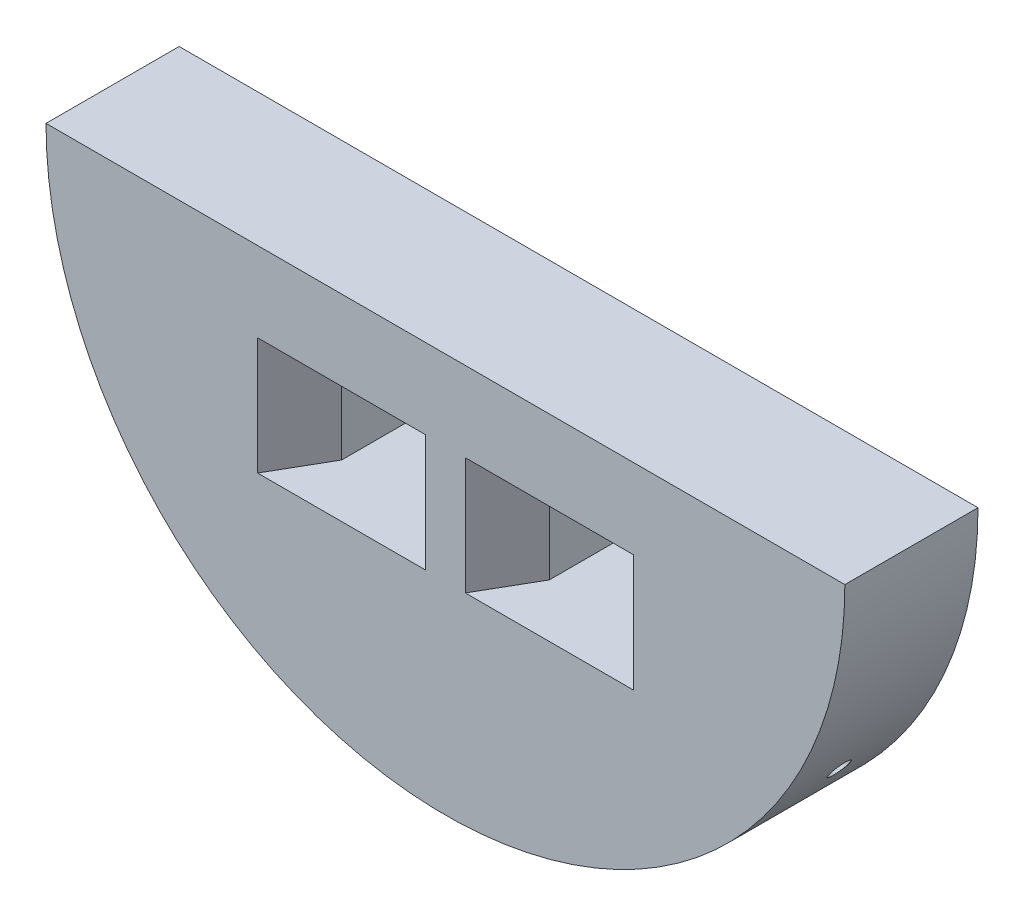
SolidWorks part; units mm, degrees
ref_plane "Front Plane" through (0, 0, 0) normal (0, 0, 1) x (1, 0, 0)
ref_plane "Top Plane" through (0, 0, 0) normal (0, 1, 0) x (1, 0, 0)
ref_plane "Right Plane" through (0, 0, 0) normal (1, 0, 0) x (0, 0, -1)
sketch "Sketch1" plane through (0, 0, 0) normal (0, 0, 1) x (1, 0, 0)
  line L0 (-150, 0) -> (0, 0)
  line L3 (-65.5, -37) -> (-45.5, -37)
  line L4 (-65.5, -37) -> (-65.5, -15)
  line L5 (-65.5, -15) -> (-45.5, -15)
  line L6 (-45.5, -37) -> (-45.5, -15)
  line L7 (-104.5, -37) -> (-84.5, -37)
  line L8 (-104.5, -37) -> (-104.5, -15)
  line L9 (-104.5, -15) -> (-84.5, -15)
  line L10 (-84.5, -37) -> (-84.5, -15)
  arc A1 (-150, 0) -> (0, 0) centre (-75, 0) ccw
  point P0 (-94.5, -15)
  point P13 (-55.5, -15)
  dimension "D1" = 19.5
  dimension "D7" = 75
  dimension "D2" = 15
  dimension "D3" = 19.5
  dimension "D4" = 20
  dimension "D5" = 22
extrude "Boss-Extrude1" add sketch "Sketch1" along normal blind 25
hole_wizard "Ø4.0mm Dowel Hole2" positions "3DSketch2" profile "Sketch4" hole size "Ø4.0" standard "ANSI Metric"
sketch3d "3DSketch2"
  line L2 (0, 0, 25) -> (0, 0, 0) construction
  line L4 (0, 0, 25) -> (0, 0, 0) construction
  line L5 (0, 0, 12.5) -> (-13.5636, -43.0182, 12.5) construction
  line L8 (-75, 0, 0) -> (-75, 0, 25) construction
  line L9 (0, 0, 0) -> (-150, 0, 0) construction
  line L10 (0, 0, 25) -> (-150, 0, 25) construction
  line L12 (-75, 0, 12.5) -> (-13.5636, -43.0182, 12.5) construction
  line L16 (-75, 0, 12.5) -> (0, 0, 12.5) construction
  point P0 (-13.5636, -43.0182, 12.5)
  point P16 (-13.5636, -43.0182, 12.5)
  point P23 (-13.5636, -43.0182, 12.5)
  point P25 (-13.5636, -43.0182, 12.5)
  dimension "D1" = 35
sketch "Sketch4" plane through (-13.5636, -43.0182, 12.5) normal (0, 0, 1) x (0.5736, 0.8192, 0)
  line L0 (0, 0) -> (0, 17.2017)
  line L1 (0, 17.2017) -> (2, 16)
  line L2 (2, 16) -> (2, 0.025)
  line L3 (2, 0.025) -> (2.025, 0)
  line L5 (2.025, 0) -> (0, 0)
  line L6 (-2, 0.025) -> (-2.025, 0) construction
  line L10 (0, 17.2017) -> (-2, 16) construction
  line L11 (0, -6.35) -> (0, 107.95) construction
  dimension "Hole Dia." = 4
  dimension "Hole Depth" = 16
  dimension "Near C'Sink Dia." = 4.05
  dimension "Near C'Sink Angle" = 90
  dimension "Drill Angle" = 118
pattern_circular "CirPattern1" count 5 over 110 about axis through (-75, 0, 0) along (0, 0, 1) of "Ø4.0mm Dowel Hole2" reverse direction yes
chamfer "Chamfer1" distance 15 angle 30 2 edges at (-94.5, -15, 0) (-55.5, -15, 0) first distance on face at (-94.5, -15, 12.5) first distance on face at (-55.5, -15, 12.5)
chamfer "Chamfer3" distance 10 angle 30 4 edges at (-104.5, -26, 25) (-84.5, -26, 25) (-45.5, -26, 25) (-65.5, -26, 25) first distance on face at (-104.5, -22.0679, 13) first distance on face at (-84.5, -22.0679, 13) first distance on face at (-45.5, -22.0679, 13) first distance on face at (-65.5, -22.0679, 13)
